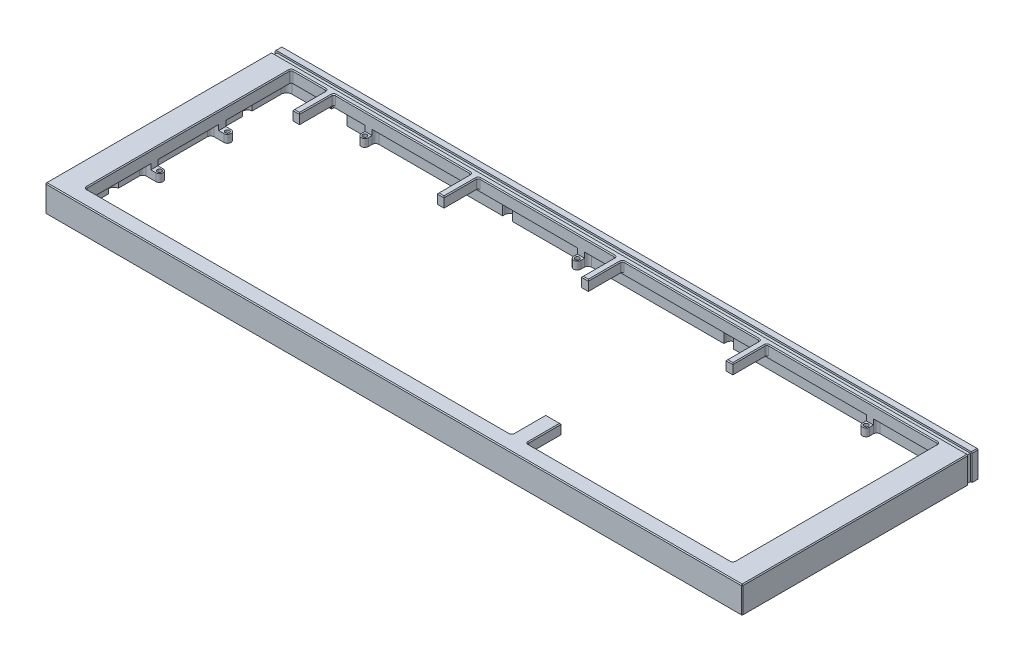
SolidWorks part; units mm, degrees
material "6061-T6 (SS)"
ref_plane "Front Plane" through (0, 0, 0) normal (0, 0, 1) x (1, 0, 0)
ref_plane "Top Plane" through (0, 0, 0) normal (0, 1, 0) x (1, 0, 0)
ref_plane "Right Plane" through (0, 0, 0) normal (1, 0, 0) x (0, 0, -1)
sketch "Sketch1" plane through (0, 0, 0) normal (0, 1, 0) x (1, 0, 0)
  line L1 (0, 0) -> (390.74, 0)
  line L2 (0, 0) -> (0, 132.7)
  line L3 (0, 132.7) -> (390.74, 132.7)
  line L4 (390.74, 0) -> (390.74, 132.7)
  line L5 (13.92, 124) -> (376.82, 124)
  line L6 (13.92, 124) -> (13.92, 8.7)
  line L7 (13.92, 8.7) -> (376.82, 8.7)
  line L8 (376.82, 124) -> (376.82, 8.7)
  point P9 (195.37, 124)
  point P10 (195.37, 132.7)
  point P11 (13.92, 66.35)
  point P12 (0, 66.35)
  dimension "D1" = 362.9
  dimension "D2" = 115.3
  dimension "D3" = 8.7
  dimension "D4" = 13.92
extrude "Main Body" add sketch "Sketch1" along normal blind 14.8
sketch "Sketch2" plane through (0, 0, 0) normal (0, -1, 0) x (1, 0, 0)
  line L0 (390.74, -132.7) -> (0, -132.7) construction
  line L1 (388.74, -130.7) -> (2, -130.7)
  line L2 (388.74, -130.7) -> (388.74, -2)
  line L3 (388.74, -2) -> (2, -2)
  line L4 (2, -130.7) -> (2, -2)
  line L5 (390.74, 0) -> (390.74, -132.7) construction
  point P4 (195.37, -130.7)
  point P7 (195.37, -132.7)
  point P8 (388.74, -66.35)
  point P11 (390.74, -66.35)
  dimension "D1" = 2
  dimension "D2" = 2
extrude "Alignment Guide" cut sketch "Sketch2" against normal blind 1 contours L2 L1 L4 L3
sketch "Sketch3" plane through (0, 14.8, 0) normal (0, 1, 0) x (1, 0, 0)
  line L0 (13.92, 8.7) -> (376.82, 8.7) construction
  line L1 (252.82, 27.8) -> (261.52, 27.8)
  line L2 (252.82, 27.8) -> (252.82, 8.7)
  line L3 (252.82, 8.7) -> (261.52, 8.7)
  line L4 (261.52, 27.8) -> (261.52, 8.7)
  line L5 (376.82, 8.7) -> (376.82, 124) construction
  line L6 (376.82, 124) -> (13.92, 124) construction
  line L7 (33.92, 124) -> (37.72, 124)
  line L8 (33.92, 124) -> (33.92, 104.9)
  line L9 (33.92, 104.9) -> (37.72, 104.9)
  line L10 (37.72, 124) -> (37.72, 104.9)
  line L11 (13.92, 124) -> (13.92, 8.7) construction
  line L12 (114.92, 124) -> (118.72, 124)
  line L13 (114.92, 124) -> (114.92, 104.9)
  line L14 (114.92, 104.9) -> (118.72, 104.9)
  line L15 (118.72, 124) -> (118.72, 104.9)
  line L16 (195.82, 124) -> (199.62, 124)
  line L17 (195.82, 124) -> (195.82, 104.9)
  line L18 (195.82, 104.9) -> (199.62, 104.9)
  line L19 (199.62, 124) -> (199.62, 104.9)
  line L20 (276.82, 124) -> (280.62, 124)
  line L21 (276.82, 124) -> (276.82, 104.9)
  line L22 (276.82, 104.9) -> (280.62, 104.9)
  line L23 (280.62, 124) -> (280.62, 104.9)
  point P8 (257.17, 8.7)
  dimension "D1" = 115.3
  dimension "D2" = 124
  dimension "D3" = 19.1
  dimension "D4" = 3.8
  dimension "D5" = 19.1
  dimension "D6" = 77.2
  dimension "D7" = 77.1
  dimension "D8" = 77.2
  dimension "D9" = 20
extrude "Blockers" add sketch "Sketch3" against normal blind 5.5
fillet "Fillet5" radius 1 14 edges at (280.62, 12.05, -124) (276.82, 12.05, -124) (195.82, 12.05, -124) (199.62, 12.05, -124) (118.72, 12.05, -124) (114.92, 12.05, -124) (33.92, 12.05, -124) (37.72, 12.05, -124) (13.92, 7.9, -124) (13.92, 7.9, -8.7) (252.82, 12.05, -8.7) (261.52, 12.05, -8.7) (376.82, 7.9, -8.7) (376.82, 7.9, -124)
sketch "Sketch4" plane through (0, 1, 0) normal (0, -1, 0) x (1, 0, 0)
  line L0 (0, 0) -> (390.74, 0) construction
  line L1 (381.27, -125.9) -> (9.47, -125.9)
  line L2 (381.27, -125.9) -> (381.27, -6.8)
  line L3 (381.27, -6.8) -> (9.47, -6.8)
  line L4 (9.47, -125.9) -> (9.47, -6.8)
  line L5 (390.74, 0) -> (390.74, -132.7) construction
  point P4 (195.37, -6.8)
  point P7 (195.37, 0)
  point P8 (381.27, -66.35)
  point P11 (390.74, -66.35)
  dimension "D1" = 119.1
  dimension "D2" = 371.8
extrude "PCB Cutout" cut sketch "Sketch4" against normal offset from surface (7.3 mm away) 6.5 up to face at (195.37, 14.8, -66.35)
fillet "Fillet4" radius 3 8 edges at (9.47, 4.65, -6.8) (9.47, 4.65, -125.9) (381.27, 4.65, -125.9) (381.27, 4.65, -6.8) (2, 0.5, -130.7) (2, 0.5, -2) (388.74, 0.5, -2) (388.74, 0.5, -130.7)
sketch "Sketch6" plane through (0, 1, 0) normal (0, -1, 0) x (1, 0, 0)
  line L0 (381.27, -9.8) -> (381.27, -122.9) construction
  line L1 (254.62, -127.1) -> (260.12, -127.1)
  line L2 (254.62, -127.1) -> (254.62, -125.9)
  line L3 (254.62, -125.9) -> (260.12, -125.9)
  line L4 (260.12, -127.1) -> (260.12, -125.9)
  line L5 (12.47, -125.9) -> (378.27, -125.9) construction
  line L11 (378.27, -6.8) -> (12.47, -6.8) construction
  line L16 (260.12, -6.8) -> (254.62, -6.8)
  line L17 (260.12, -6.8) -> (260.12, -4.8)
  line L18 (260.12, -4.8) -> (254.62, -4.8)
  line L19 (254.62, -6.8) -> (254.62, -4.8)
  line L21 (0, 0) -> (390.74, 0) construction
  line L24 (390.74, -66.35) -> (195.37, -66.35) construction
  line L25 (390.74, 0) -> (390.74, -132.7) construction
  line L26 (328.6755, -66.35) -> (328.6755, -130.7) construction
  line L27 (385.74, -130.7) -> (5, -130.7) construction
  line L28 (328.6755, -66.35) -> (328.6755, -8.7) construction
  line L29 (375.82, -8.7) -> (14.92, -8.7) construction
  line L55 (390.74, -132.7) -> (0, -132.7) construction
  line L56 (195.37, -132.7) -> (195.37, 0) construction
  line L57 (136.12, -6.8) -> (136.12, -4.8)
  line L58 (130.62, -4.8) -> (136.12, -4.8)
  line L59 (130.62, -6.8) -> (130.62, -4.8)
  line L60 (130.62, -6.8) -> (136.12, -6.8)
  line L61 (130.62, -127.1) -> (130.62, -125.9)
  line L62 (136.12, -125.9) -> (130.62, -125.9)
  line L63 (136.12, -127.1) -> (136.12, -125.9)
  line L64 (136.12, -127.1) -> (130.62, -127.1)
  circle A0 centre (381.07, -103.85) radius 2.75
  circle A1 centre (381.07, -28.85) radius 2.75
  circle A2 centre (257.37, -4.8) radius 2.75
  circle A3 centre (257.37, -127.1) radius 2.75
  circle A8 centre (133.37, -4.8) radius 2.75
  circle A9 centre (9.67, -28.85) radius 2.75
  circle A10 centre (9.67, -103.85) radius 2.75
  circle A11 centre (133.37, -127.1) radius 2.75
  point P25 (195.37, -66.35)
  point P32 (257.37, -125.9)
  point P33 (257.37, -6.8)
  line M17 (12.47, -6.8) -> (378.27, -6.8)
  line M18 (381.27, -9.8) -> (381.27, -122.9)
  line M19 (378.27, -125.9) -> (12.47, -125.9)
  line M20 (9.47, -122.9) -> (9.47, -9.8)
  dimension "D4" = 5.5
  dimension "D5" = 62
  dimension "D1" = 37.5
  dimension "D2" = 4.8
  dimension "D3" = 37.5
  dimension "D6" = 0.2
  dimension "D7" = 5.6
extrude "PlateTabs" cut sketch "Sketch6" against normal up to surface (7.3 mm away) contours A0 M18 | A1 M18 | A2 L19 M17 | L16 A2 L18 | A2 L17 M17 | L18 A2 | L1 A3 | L1 A3 L3 | A3 L2 M19 | A11 L64 | A11 L64 L62 | A10 M20 | A9 M20 | A8 L58 | A8 L60 L58 | A3 L4 M19 | A8 L59 M17 | L57 A8 M17 | A11 L63 M19 | L61 A11 M19 | A11 | L59 L58 L57 L60 | A3 region at (257.37, 1, -126.5102) region at (136.0381, 1, -126.1969) region at (257.37, 1, -128.2671) region at (254.7019, 1, -126.1969) region at (260.0381, 1, -126.1969) region at (133.37, 1, -126.5102) region at (133.37, 1, -128.2671) region at (130.7019, 1, -126.1969) region at (135.8701, 1, -6.317) region at (259.8701, 1, -6.317) region at (257.37, 1, -5.7445) region at (257.37, 1, -3.6329) region at (254.8699, 1, -6.317) region at (133.37, 1, -5.7445) region at (133.37, 1, -3.6329) region at (130.8699, 1, -6.317) region at (382.3459, 1, -103.85) region at (382.3459, 1, -28.85) region at (8.3941, 1, -103.85) region at (8.3941, 1, -28.85) up to face at (195.37, 8.3, -66.35)
sketch "Sketch9" plane through (0, 0, -132.7) normal (0, 0, -1) x (-1, 0, 0)
  line L1 (-41.8, 0) -> (-29.8, 0)
  line L2 (-41.8, 0) -> (-41.8, 3.2)
  line L3 (-41.8, 3.2) -> (-29.8, 3.2)
  line L4 (-29.8, 0) -> (-29.8, 3.2)
  line L5 (-390.74, 0) -> (0, 0) construction
  line L7 (0, 14.8) -> (0, 0) construction
  point P6 (-35.8, 3.2)
  dimension "D1" = 3.2
  dimension "D3" = 12
  dimension "D4" = 35.8
extrude "USB Cutout" cut sketch "Sketch9" against normal up to surface (8.7 mm away) up to face at (164.89, 11.95, -124)
sketch "Sketch11" plane through (0, 0, -125.9) normal (0, 0, 1) x (1, 0, 0)
  line L0 (130.62, 8.3) -> (12.47, 8.3) construction
  line L1 (43.3, 1) -> (28.3, 1)
  line L2 (43.3, 1) -> (43.3, 8.3)
  line L3 (43.3, 8.3) -> (28.3, 8.3)
  line L4 (28.3, 1) -> (28.3, 8.3)
  line L7 (12.47, 1) -> (29.8, 1) construction
  line L8 (29.8, 3.2) -> (41.8, 3.2) construction
  point P8 (35.8, 1)
  point P18 (35.8, 3.2)
  dimension "D1" = 15
extrude "PCB Clearance" cut sketch "Sketch11" against normal blind 3.9
fillet "Fillet7" radius 2.5 2 edges at (28.3, 4.65, -129.8) (43.3, 4.65, -129.8)
sketch "Sketch12" plane through (0, 8.3, 0) normal (0, -1, 0) x (1, 0, 0)
  line L0 (195.37, -132.7) -> (195.37, 0) construction
  line L2 (14.92, -124) -> (375.82, -124) construction
  line L3 (0, 0) -> (390.74, 0) construction
  line L5 (390.74, -132.7) -> (41.8, -132.7) construction
  line L8 (376.82, -123) -> (376.82, -9.7) construction
  arc A0 (381.27, -31.5927) -> (381.27, -26.1073) centre (381.07, -28.85) ccw construction
  arc A1 (381.27, -106.5927) -> (381.27, -101.1073) centre (381.07, -103.85) ccw construction
  point P0 (257.37, -127.1)
  point P1 (381.42, -103.85)
  point P2 (381.42, -28.85)
  point P3 (257.37, -4.85)
  point P7 (195.37, -66.35)
  point P8 (133.37, -4.85)
  point P10 (9.32, -28.85)
  point P14 (9.32, -103.85)
  point P16 (133.37, -127.1)
  point P34 (383.82, -28.85)
  point P39 (383.82, -103.85)
  dimension "D1" = 3.1
  dimension "D2" = 61.5
  dimension "D3" = 4.6
  dimension "D4" = 62
chamfer "Chamfer1" distance 0.5 46 edges at (14.2129, 14.8, -8.9929) (133.37, 14.8, -8.7) (252.5271, 14.8, -8.9929) (252.82, 14.8, -18.75) (257.17, 14.8, -27.8) (261.52, 14.8, -18.75) (261.8129, 14.8, -8.9929) (319.17, 14.8, -8.7) (376.5271, 14.8, -8.9929) (376.82, 14.8, -66.35) (376.5271, 14.8, -123.7071) (328.72, 14.8, -124) (280.9129, 14.8, -123.7071) (280.62, 14.8, -113.95) (278.72, 14.8, -104.9) (276.82, 14.8, -113.95) (276.5271, 14.8, -123.7071) (238.22, 14.8, -124) (199.9129, 14.8, -123.7071) (199.62, 14.8, -113.95) (197.72, 14.8, -104.9) (195.82, 14.8, -113.95) (195.5271, 14.8, -123.7071) (157.27, 14.8, -124) (119.0129, 14.8, -123.7071) (118.72, 14.8, -113.95) (116.82, 14.8, -104.9) (114.92, 14.8, -113.95) (114.6271, 14.8, -123.7071) (76.32, 14.8, -124) (38.0129, 14.8, -123.7071) (37.72, 14.8, -113.95) (35.82, 14.8, -104.9) (33.92, 14.8, -113.95) (33.6271, 14.8, -123.7071) (23.92, 14.8, -124) (14.2129, 14.8, -123.7071) (13.92, 14.8, -66.35) (195.37, 14.8, -132.7) (390.74, 14.8, -66.35) (195.37, 14.8, 0) (0, 14.8, -66.35) (390.74, 7.4, -132.7) (390.74, 7.4, 0) (0, 7.4, -132.7) (0, 7.4, 0)
chamfer "Chamfer2" distance 0.1 5 edges at (390.74, 0, -66.35) (195.37, 0, 0) (0, 0, -66.35) (15.15, 0, -132.7) (216.02, 0, -132.7)
sketch "Sketch27" plane through (0, 14.8, 0) normal (0, 1, 0) x (1, 0, 0)
  line L0 (0, 0.5) -> (0, 132.2) construction
  line L1 (0, 128.95) -> (390.74, 128.95)
  line L2 (0, 128.95) -> (0, 126.45)
  line L3 (0, 126.45) -> (390.74, 126.45)
  line L4 (390.74, 128.95) -> (390.74, 126.45)
  line L5 (390.74, 132.2) -> (390.74, 0.5) construction
  line L6 (372.9261, 132.2) -> (372.9261, 124.5) construction
  line L7 (390.24, 132.2) -> (0.5, 132.2) construction
  line L9 (281.62, 124.5) -> (375.82, 124.5) construction
  point P14 (390.74, 127.7)
  dimension "D1" = 2.5
  dimension "D2" = 3.2
extrude "Cut-Extrude11" cut sketch "Sketch27" against normal blind 1
sketch "Sketch28" plane through (0, 13.8, 0) normal (0, 1, 0) x (1, 0, 0)
  line L1 (0, 128.95) -> (1, 128.95)
  line L2 (0, 128.95) -> (0, 126.45)
  line L3 (0, 126.45) -> (1, 126.45)
  line L4 (1, 128.95) -> (1, 126.45)
  line L5 (389.74, 128.95) -> (390.74, 128.95)
  line L6 (389.74, 128.95) -> (389.74, 126.45)
  line L7 (389.74, 126.45) -> (390.74, 126.45)
  line L8 (390.74, 128.95) -> (390.74, 126.45)
  line L9 (390.74, 128.95) -> (0, 128.95) construction
  line L10 (0, 126.45) -> (390.74, 126.45) construction
  dimension "D1" = 1
  dimension "D2" = 1
extrude "Cut-Extrude12" cut sketch "Sketch28" against normal through all
sketch "Sketch21" [suppressed] plane through (0, 14.8, 0) normal (0, 1, 0) x (1, 0, 0)
  line L0 (0.5, 132.7) -> (390.24, 132.7) construction
  line L1 (382.53, 132.7) -> (385.03, 132.7)
  line L2 (382.53, 132.7) -> (382.53, 72.7)
  line L3 (382.53, 72.7) -> (385.03, 72.7)
  line L4 (385.03, 132.7) -> (385.03, 72.7)
  line L5 (390.74, 132.2) -> (390.74, 129.7) construction
  line L6 (390.74, 129.1) -> (294.74, 129.1)
  line L7 (390.74, 129.1) -> (390.74, 127.6)
  line L8 (390.74, 127.6) -> (294.74, 127.6)
  line L9 (294.74, 129.1) -> (294.74, 127.6)
  line L10 (362.9081, 132.2) -> (362.9081, 124.5) construction
  line L11 (390.24, 132.2) -> (0.5, 132.2) construction
  line L12 (281.62, 124.5) -> (375.82, 124.5) construction
  line L13 (365.5702, 129.1) -> (365.5702, 127.6) construction
  line L14 (377.32, 119.5259) -> (390.24, 119.5259) construction
  line L15 (377.32, 123) -> (377.32, 9.7) construction
  line L16 (390.24, 0.5) -> (390.24, 127.2) construction
  line L17 (382.53, 116.0504) -> (385.03, 116.0504) construction
  point P28 (383.78, 116.0504)
  point P29 (383.78, 119.5259)
  point P30 (365.5702, 128.35)
  point P31 (362.9081, 128.35)
  dimension "D1" = 2.5
  dimension "D2" = 1.5
  dimension "D3" = 60
  dimension "D4" = 96
extrude "Cut-Extrude5" [suppressed] cut sketch "Sketch21" against normal blind 1 contours L4 L3 L2 L1 | L8 L9 L6 L7
sketch "Sketch23" [suppressed] plane through (390.74, 0, 0) normal (1, 0, 0) x (0, 0, -1)
  line L0 (129.1, 13.8) -> (129.1, 14.3) construction
  line L1 (127.6, 13.8) -> (129.1, 13.8)
  line L2 (127.6, 13.8) -> (127.6, 0)
  line L3 (127.6, 0) -> (129.1, 0)
  line L4 (129.1, 13.8) -> (129.1, 0)
extrude "Cut-Extrude6" [suppressed] cut sketch "Sketch23" against normal blind 1
sketch "Sketch19" plane through (0, 14.8, 0) normal (0, 1, 0) x (1, 0, 0)
  line L0 (0.5, 132.7) -> (390.24, 132.7) construction
  line L1 (5.46, 132.7) -> (8.46, 132.7)
  line L2 (5.46, 132.7) -> (5.46, 0)
  line L3 (5.46, 0) -> (8.46, 0)
  line L4 (8.46, 132.7) -> (8.46, 0)
  line L7 (382.28, 132.7) -> (385.28, 132.7)
  line L8 (382.28, 132.7) -> (382.28, 0)
  line L9 (382.28, 0) -> (385.28, 0)
  line L10 (385.28, 132.7) -> (385.28, 0)
  line L11 (390.24, 0) -> (0.5, 0) construction
  line L12 (377.32, 110.209) -> (390.24, 110.209) construction
  line L13 (377.32, 123) -> (377.32, 9.7) construction
  line L14 (390.24, 0.5) -> (390.24, 126.45) construction
  line L15 (382.28, 106.8719) -> (385.28, 106.8719) construction
  line L16 (0.5, 106.8719) -> (13.42, 106.8719) construction
  line L17 (0.5, 132.2) -> (0.5, 128.95) construction
  line L18 (13.42, 9.7) -> (13.42, 123) construction
  line L19 (5.46, 102.7297) -> (8.46, 102.7297) construction
  point P12 (383.78, 106.8719)
  point P14 (383.78, 110.209)
  point P30 (6.96, 102.7297)
  point P31 (6.96, 106.8719)
  dimension "D1" = 3
  dimension "D2" = 3
extrude "Cut-Extrude3" [suppressed] cut sketch "Sketch19" against normal blind 1
sketch "Sketch17" plane through (0, 14.8, 0) normal (0, 1, 0) x (1, 0, 0)
  line L0 (390.24, 0.5) -> (390.24, 126.45) construction
  line L1 (5.71, 129.6) -> (385.03, 129.6)
  line L2 (5.71, 129.6) -> (5.71, -2.65)
  line L3 (5.71, -2.65) -> (385.03, -2.65)
  line L4 (385.03, 129.6) -> (385.03, -2.65)
  line L5 (8.21, 127.1) -> (382.53, 127.1)
  line L6 (8.21, 127.1) -> (8.21, -0.15)
  line L7 (8.21, -0.15) -> (382.53, -0.15)
  line L8 (382.53, 127.1) -> (382.53, -0.15)
  line L9 (390.24, 132.2) -> (0.5, 132.2) construction
  line L10 (21.2533, 132.2) -> (21.2533, 124.5) construction
  line L11 (14.92, 124.5) -> (32.92, 124.5) construction
  line L12 (25.2757, 129.6) -> (25.2757, 127.1) construction
  line L13 (0.5, 116.1326) -> (13.42, 116.1326) construction
  line L14 (0.5, 132.2) -> (0.5, 128.95) construction
  line L15 (13.42, 9.7) -> (13.42, 123) construction
  line L16 (5.71, 120.1548) -> (8.21, 120.1548) construction
  point P8 (382.53, 63.475)
  point P9 (385.03, 63.475)
  point P12 (390.24, 63.475)
  point P13 (195.37, 129.6)
  point P14 (195.37, 127.1)
  point P17 (195.37, 132.2)
  point P24 (25.2757, 128.35)
  point P25 (21.2533, 128.35)
  point P34 (6.96, 116.1326)
  point P35 (6.96, 120.1548)
  dimension "D1" = 2.5
  dimension "D2" = 2.5
extrude "Cut-Extrude1" [suppressed] cut sketch "Sketch17" against normal blind 1
hole_wizard "M2x0.4 Tapped Hole1" positions "3DSketch3" profile "Sketch31" tap size "M2x0.4" standard "ANSI Metric"
sketch3d "3DSketch3"
  point P0 (381.42, 8.3, -103.85)
  point P3 (381.42, 8.3, -28.85)
  point P7 (257.37, 8.3, -4.85)
  point P10 (133.37, 8.3, -4.85)
  point P13 (9.32, 8.3, -28.85)
  point P16 (9.32, 8.3, -103.85)
  point P19 (133.37, 8.3, -127.1)
  point P22 (257.37, 8.3, -127.1)
sketch "Sketch31" plane through (381.42, 8.3, -103.85) normal (1, 0, 0) x (0, 0, -1)
  line L0 (0, 0) -> (0, 4.4807)
  line L1 (0, 4.4807) -> (0.8, 4)
  line L2 (0.8, 4) -> (0.8, 0)
  line L5 (0.8, 0) -> (0, 0)
  line L10 (0, 4.4807) -> (-0.8, 4) construction
  line L11 (0, -6.35) -> (0, 107.95) construction
  dimension "Tap Drill Dia." = 1.6
  dimension "Tap Drill Depth" = 4
  dimension "Drill Angle" = 118
cosmetic thread "Hole Thread19" parameters "D1"=4, "D2"=2
cosmetic thread "Hole Thread20" parameters "D1"=4, "D2"=2
cosmetic thread "Hole Thread21" parameters "D1"=4, "D2"=2
cosmetic thread "Hole Thread22" parameters "D1"=4, "D2"=2
cosmetic thread "Hole Thread23" parameters "D1"=4, "D2"=2
cosmetic thread "Hole Thread24" parameters "D1"=4, "D2"=2
cosmetic thread "Hole Thread25" parameters "D1"=4, "D2"=2
cosmetic thread "Hole Thread26" parameters "D1"=4, "D2"=2
fillet "Fillet8" radius 0.1 9 edges at (213.77, 0, -130.7) (387.8613, 0, -129.8213) (17.4, 0, -130.7) (2.8787, 0, -129.8213) (2, 0, -66.35) (2.8787, 0, -2.8787) (195.37, 0, -2) (387.8613, 0, -2.8787) (388.74, 0, -66.35)
sketch "Sketch32" plane through (0, 1, 0) normal (0, -1, 0) x (1, 0, 0)
  line L1 (0, -126.45) -> (0, -0.5) construction
  line L3 (378.27, -125.9) -> (260.12, -125.9) construction
  line L4 (340.3, -121.9) -> (336.3, -121.9)
  line L5 (340.3, -121.9) -> (340.3, -125.9)
  line L6 (340.3, -125.9) -> (336.3, -125.9)
  line L7 (336.3, -121.9) -> (336.3, -125.9)
  line L8 (254.62, -125.9) -> (136.12, -125.9) construction
  line L9 (178.4, -121.9) -> (174.4, -121.9)
  line L10 (178.4, -121.9) -> (178.4, -125.9)
  line L11 (178.4, -125.9) -> (174.4, -125.9)
  line L12 (174.4, -121.9) -> (174.4, -125.9)
  line L13 (43.3, -125.9) -> (130.62, -125.9) construction
  line L14 (59.3, -121.9) -> (55.3, -121.9)
  line L15 (59.3, -121.9) -> (59.3, -125.9)
  line L16 (59.3, -125.9) -> (55.3, -125.9)
  line L17 (55.3, -121.9) -> (55.3, -125.9)
  line L18 (9.47, -31.5927) -> (9.47, -101.1073) construction
  line L19 (16.8, -83.4) -> (9.47, -83.4)
  line L20 (16.8, -83.4) -> (16.8, -87.4)
  line L21 (16.8, -87.4) -> (9.47, -87.4)
  line L22 (9.47, -83.4) -> (9.47, -87.4)
  line L23 (12.47, -6.8) -> (130.62, -6.8) construction
  line L24 (16.8, -45.3) -> (9.47, -45.3)
  line L25 (16.8, -45.3) -> (16.8, -49.3)
  line L26 (16.8, -49.3) -> (9.47, -49.3)
  line L27 (9.47, -45.3) -> (9.47, -49.3)
  line L28 (87.9, -11.6) -> (83.9, -11.6)
  line L29 (87.9, -11.6) -> (87.9, -6.8)
  line L30 (87.9, -6.8) -> (83.9, -6.8)
  line L31 (83.9, -11.6) -> (83.9, -6.8)
  line L32 (254.62, -6.8) -> (136.12, -6.8) construction
  line L33 (158.5, -11.6) -> (154.5, -11.6)
  line L34 (158.5, -11.6) -> (158.5, -6.8)
  line L35 (158.5, -6.8) -> (154.5, -6.8)
  line L36 (154.5, -11.6) -> (154.5, -6.8)
  line L37 (378.27, -6.8) -> (260.12, -6.8) construction
  line L38 (302.2, -11.6) -> (298.2, -11.6)
  line L39 (302.2, -11.6) -> (302.2, -6.8)
  line L40 (302.2, -6.8) -> (298.2, -6.8)
  line L41 (298.2, -11.6) -> (298.2, -6.8)
  line L42 (195.37, 0) -> (195.37, -132.6) construction
  line L43 (0.5, 0) -> (390.24, 0) construction
  line L44 (381.27, -45.3) -> (381.27, -49.3)
  line L45 (373.94, -49.3) -> (381.27, -49.3)
  line L46 (373.94, -45.3) -> (373.94, -49.3)
  line L47 (373.94, -45.3) -> (381.27, -45.3)
  line L48 (381.27, -83.4) -> (381.27, -87.4)
  line L49 (373.94, -87.4) -> (381.27, -87.4)
  line L50 (373.94, -83.4) -> (373.94, -87.4)
  line L51 (373.94, -83.4) -> (381.27, -83.4)
  line L52 (41.8, -132.6) -> (390.34, -132.6) construction
  line L53 (29.8, -132.7) -> (41.8, -132.7) construction
  circle A0 centre (338.3, -121.9) radius 2
  circle A1 centre (176.4, -121.9) radius 2
  circle A2 centre (57.3, -121.9) radius 2
  circle A3 centre (16.8, -85.4) radius 2
  circle A4 centre (16.8, -47.3) radius 2
  circle A5 centre (85.9, -11.6) radius 2
  circle A6 centre (156.5, -11.6) radius 2
  circle A7 centre (300.2, -11.6) radius 2
  circle A8 centre (373.94, -47.3) radius 2
  circle A9 centre (373.94, -85.4) radius 2
  dimension "D1" = 4
  dimension "D2" = 10.8
  dimension "D3" = 57.3
  dimension "D4" = 119.1
  dimension "D5" = 161.9
  dimension "D6" = 36.5
  dimension "D7" = 38.1
  dimension "D8" = 28.6
  dimension "D9" = 70.6
  dimension "D10" = 143.7
  dimension "D11" = 40.5
  dimension "D12" = 110.3
extrude "Boss-Extrude1" add sketch "Sketch32" against normal offset from surface (4.3 mm away) 3 contours A1 | L12 L11 L10 L9 | A0 | L5 L6 L7 L4 | A9 | L51 L48 L49 L50 | L47 L44 L45 L46 | A8 | L41 L40 L39 L38 | A7 | A6 | L36 L35 L34 L33 | A5 | L31 L30 L29 L28 | A4 | L26 L27 L24 L25 | A3 | L19 L22 L21 L20 | A2 | L15 L16 L17 L14 up to face at (381.42, 8.3, -104.65)
sketch "Sketch33" plane through (0, 8.3, 0) normal (0, -1, 0) x (1, 0, 0)
  line L0 (373.94, -83.4) -> (381.27, -83.4) construction
  line L1 (381.27, -87.4) -> (376.82, -87.4)
  line L2 (381.27, -87.4) -> (381.27, -83.4)
  line L3 (381.27, -83.4) -> (376.82, -83.4)
  line L4 (376.82, -87.4) -> (376.82, -83.4)
  line L5 (376.82, -123) -> (376.82, -9.7) construction
  line L6 (373.94, -45.3) -> (381.27, -45.3) construction
  line L7 (381.27, -49.3) -> (376.82, -49.3)
  line L8 (381.27, -49.3) -> (381.27, -45.3)
  line L9 (381.27, -45.3) -> (376.82, -45.3)
  line L10 (376.82, -49.3) -> (376.82, -45.3)
  line L11 (375.82, -8.7) -> (14.92, -8.7) construction
  line L12 (302.2, -6.8) -> (298.2, -6.8)
  line L13 (302.2, -6.8) -> (302.2, -8.7)
  line L14 (302.2, -8.7) -> (298.2, -8.7)
  line L15 (298.2, -6.8) -> (298.2, -8.7)
  line L16 (298.2, -11.6) -> (298.2, -6.8) construction
  line L17 (154.5, -11.6) -> (154.5, -6.8) construction
  line L18 (158.5, -6.8) -> (154.5, -6.8)
  line L19 (158.5, -6.8) -> (158.5, -8.7)
  line L20 (158.5, -8.7) -> (154.5, -8.7)
  line L21 (154.5, -6.8) -> (154.5, -8.7)
  line L22 (83.9, -11.6) -> (83.9, -6.8) construction
  line L23 (87.9, -6.8) -> (83.9, -6.8)
  line L24 (87.9, -6.8) -> (87.9, -8.7)
  line L25 (87.9, -8.7) -> (83.9, -8.7)
  line L26 (83.9, -6.8) -> (83.9, -8.7)
  line L27 (16.8, -49.3) -> (9.47, -49.3) construction
  line L28 (9.47, -45.3) -> (13.92, -45.3)
  line L29 (9.47, -45.3) -> (9.47, -49.3)
  line L30 (9.47, -49.3) -> (13.92, -49.3)
  line L31 (13.92, -45.3) -> (13.92, -49.3)
  line L32 (13.92, -9.7) -> (13.92, -123) construction
  line L33 (16.8, -87.4) -> (9.47, -87.4) construction
  line L34 (9.47, -83.4) -> (13.92, -83.4)
  line L35 (9.47, -83.4) -> (9.47, -87.4)
  line L36 (9.47, -87.4) -> (13.92, -87.4)
  line L37 (13.92, -83.4) -> (13.92, -87.4)
  line L38 (59.3, -121.9) -> (59.3, -125.9) construction
  line L39 (55.3, -125.9) -> (59.3, -125.9)
  line L40 (55.3, -125.9) -> (55.3, -124)
  line L41 (55.3, -124) -> (59.3, -124)
  line L42 (59.3, -125.9) -> (59.3, -124)
  line L43 (14.92, -124) -> (375.82, -124) construction
  line L44 (178.4, -121.9) -> (178.4, -125.9) construction
  line L45 (174.4, -125.9) -> (178.4, -125.9)
  line L46 (174.4, -125.9) -> (174.4, -124)
  line L47 (174.4, -124) -> (178.4, -124)
  line L48 (178.4, -125.9) -> (178.4, -124)
  line L49 (340.3, -121.9) -> (340.3, -125.9) construction
  line L50 (336.3, -125.9) -> (340.3, -125.9)
  line L51 (336.3, -125.9) -> (336.3, -124)
  line L52 (336.3, -124) -> (340.3, -124)
  line L53 (340.3, -125.9) -> (340.3, -124)
extrude "Boss-Extrude2" add sketch "Sketch33" along normal up to surface (3 mm away) up to face at (338.3, 5.3, -123.4)
fillet "Fillet9" radius 1.9 19 edges at (340.3, 4.65, -125.9) (336.3, 4.65, -125.9) (174.4, 4.65, -125.9) (178.4, 4.65, -125.9) (59.3, 4.65, -125.9) (55.3, 4.65, -125.9) (9.47, 4.65, -87.4) (9.47, 4.65, -83.4) (9.47, 4.65, -45.3) (9.47, 4.65, -49.3) (87.9, 4.65, -6.8) (83.9, 4.65, -6.8) (154.5, 4.65, -6.8) (158.5, 4.65, -6.8) (302.2, 4.65, -6.8) (298.2, 4.65, -6.8) (381.27, 4.65, -45.3) (381.27, 4.65, -49.3) (381.27, 4.65, -87.4)
sketch "Sketch34" plane through (0, 5.3, 0) normal (0, 1, 0) x (1, 0, 0)
  point P0 (16.8, 47.3)
  point P1 (16.8, 85.4)
  point P3 (85.9, 11.6)
  point P5 (156.5, 11.6)
  point P7 (300.2, 11.6)
  point P9 (373.94, 47.3)
  point P11 (373.94, 85.4)
  point P13 (338.3, 121.9)
  point P15 (176.4, 121.9)
  point P17 (57.3, 121.9)
hole_wizard "M2 Clearance Hole1" positions "3DSketch4" profile "Sketch35" hole size "M2" standard "ANSI Metric" end condition through all
sketch3d "3DSketch4"
  point P0 (57.3, 5.3, -121.9)
  point P3 (16.8, 5.3, -85.4)
  point P6 (16.8, 5.3, -47.3)
  point P9 (85.9, 5.3, -11.6)
  point P12 (156.5, 5.3, -11.6)
  point P15 (300.2, 5.3, -11.6)
  point P18 (373.94, 5.3, -47.3)
  point P21 (373.94, 5.3, -85.4)
  point P24 (338.3, 5.3, -121.9)
  point P27 (176.4, 5.3, -121.9)
sketch "Sketch35" plane through (57.3, 5.3, -121.9) normal (1, 0, 0) x (0, 0, 1)
  line L0 (0, 0) -> (0, 5.3)
  line L1 (0, 5.3) -> (1.2, 5.3)
  line L2 (1.2, 5.3) -> (1.2, 0)
  line L5 (1.2, 0) -> (0, 0)
  line L11 (0, -6.35) -> (0, 107.95) construction
  dimension "Thru Hole Dia." = 2.4
  dimension "Thru Hole Depth" = 5.3
